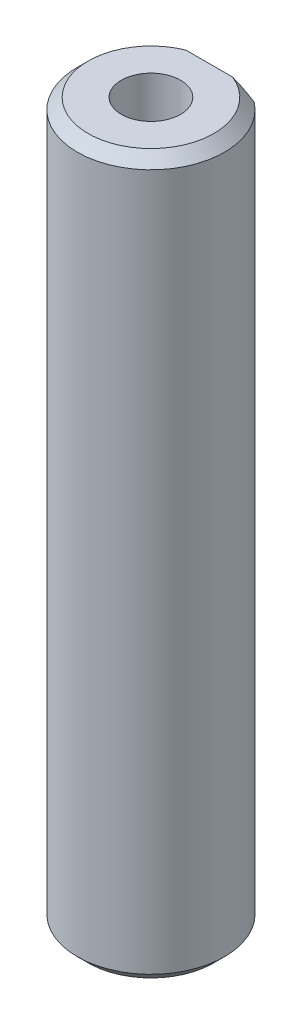
SolidWorks part; units mm, degrees
ref_plane "Front Plane" through (0, 0, 0) normal (0, 0, 1) x (1, 0, 0)
ref_plane "Top Plane" through (0, 0, 0) normal (0, 1, 0) x (1, 0, 0)
ref_plane "Right Plane" through (0, 0, 0) normal (1, 0, 0) x (0, 0, -1)
sketch "Sketch1" plane through (0, 0, 0) normal (0, 1, 0) x (1, 0, 0)
  line L0 (-2.5, 3.2496) -> (2.5, 3.2496)
  circle A0 centre (0, 0) radius 4.1
  circle A1 centre (0, 0) radius 2.6
  dimension "D1" = 8.2
  dimension "D2" = 5.2
  dimension "D3" = 5
extrude "Boss-Extrude2" add sketch "Sketch1" along normal blind 40 contours A1 | A0 A1
ref_plane "Plane1" through (0, 0, 4.1) normal (0, 0, 1) x (1, 0, 0)
sketch "Sketch2" plane through (0, 0, 4.1) normal (0, 0, 1) x (1, 0, 0)
  line L0 (0, 0) -> (0, 40) construction
  line L1 (4.1, 40) -> (-4.1, 40) construction
  circle A0 centre (0, 20) radius 1.75
  dimension "D1" = 3.5
extrude "Cut-Extrude1" cut sketch "Sketch2" along normal blind 4 from surface at -7.3496 starting at face at (0, 20, -3.2496)
hole_wizard "Ø1.0mm Dowel Hole1" positions "Sketch5" profile "Sketch6" hole size "Ø1.0" standard "AS"
sketch "Sketch5" plane through (0, 40, 0) normal (0, 1, 0) x (1, 0, 0)
  point P0 (0, 0)
sketch "Sketch6" plane through (0, 40, 0) normal (1, 0, 0) x (0, 0, 1)
  line L0 (0, 0) -> (0, 15)
  line L1 (0, 15) -> (1.65, 14.0086)
  line L2 (1.65, 14.0086) -> (1.65, 0)
  line L5 (1.65, 0) -> (0, 0)
  line L10 (0, 15) -> (-1.65, 14.0086) construction
  line L11 (0, -6.35) -> (0, 107.95) construction
  dimension "Hole Dia." = 3.3
  dimension "Hole Depth" = 15
  dimension "Drill Angle" = 118
hole_wizard "Ø1.0mm Dowel Hole2" positions "Sketch7" profile "Sketch8" hole size "Ø1.0" standard "AS"
sketch "Sketch7" plane through (0, 0, 0) normal (0, -1, 0) x (-1, 0, 0)
  point P0 (0, 0)
sketch "Sketch8" plane through (0, 0, 0) normal (1, 0, 0) x (0, 0, -1)
  line L0 (0, 0) -> (0, 15)
  line L1 (0, 15) -> (1.65, 14.0086)
  line L2 (1.65, 14.0086) -> (1.65, 0)
  line L5 (1.65, 0) -> (0, 0)
  line L10 (0, 15) -> (-1.65, 14.0086) construction
  line L11 (0, -6.35) -> (0, 107.95) construction
  dimension "Hole Dia." = 3.3
  dimension "Hole Depth" = 15
  dimension "Drill Angle" = 118
thread "Thread2" [suppressed] pitch 0.45 start angle 0, offset 0, length 10, pitch 0.45, diameter 2.9
ref_plane "Plane4" through (1.45, 1.014, 0) normal (0, 0, 1) x (1, 0, 0)
sketch "Thread Profile3" plane through (1.45, 1.014, 0) normal (0, 0, 1) x (1, 0, 0)
  line L0 (0, 0) -> (0, 0.45) construction
  line L1 (0, 0) -> (0.2436, 0.1406)
  line L2 (0.2436, 0.1406) -> (0.2436, 0.1969)
  line L3 (0.2436, 0.1969) -> (0, 0.3375)
  line L4 (0.2436, 0.1687) -> (0, 0.1687) construction
  line L11 (0, 0) -> (0, 0.3375)
  point P2 (0, 0)
  dimension "Pitch" = 0.45
  dimension "Profile_Angle" = 60
  dimension "Profile_Land" = 0.0562
  dimension "Profile_Height" = 0.2436
thread "Thread3" [suppressed] pitch 0.45 start angle 0, offset 0, length 10, pitch 0.45, diameter 2.9
ref_plane "Plane5" through (-1.45, 38.986, 0) normal (0, 0, 1) x (-1, 0, 0)
sketch "Thread Profile4" plane through (-1.45, 38.986, 0) normal (0, 0, 1) x (-1, 0, 0)
  line L0 (0, 0) -> (0, 0.45) construction
  line L1 (0, 0) -> (0.2436, 0.1406)
  line L2 (0.2436, 0.1406) -> (0.2436, 0.1969)
  line L3 (0.2436, 0.1969) -> (0, 0.3375)
  line L4 (0.2436, 0.1687) -> (0, 0.1687) construction
  line L11 (0, 0) -> (0, 0.3375)
  point P2 (0, 0)
  dimension "Pitch" = 0.45
  dimension "Profile_Angle" = 60
  dimension "Profile_Land" = 0.0562
  dimension "Profile_Height" = 0.2436
chamfer "Chamfer1" distance 0.6 angle 45 1 edges at (0, 40, 4.1)
chamfer "Chamfer2" distance 0.6 angle 45 1 edges at (0, 0, 4.1)
